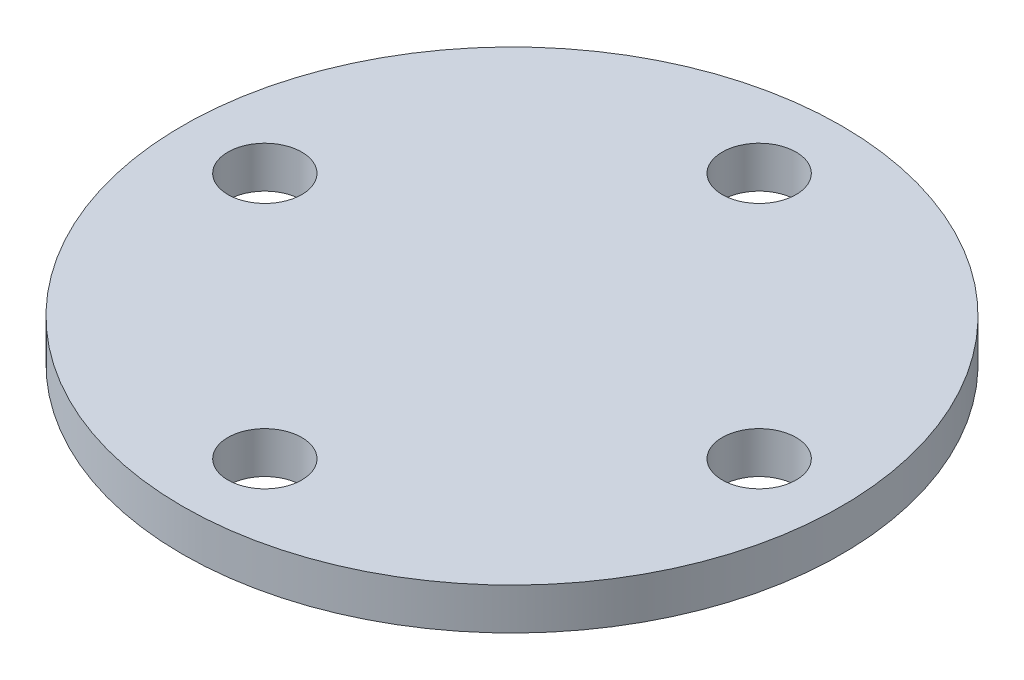
SolidWorks part; units mm, degrees
material "Custom Plastic"
ref_plane "Front Plane" through (0, 0, 0) normal (0, 0, 1) x (1, 0, 0)
ref_plane "Top Plane" through (0, 0, 0) normal (0, 1, 0) x (1, 0, 0)
ref_plane "Right Plane" through (0, 0, 0) normal (1, 0, 0) x (0, 0, -1)
sketch "Sketch1" plane through (0, 0, 0) normal (0, 1, 0) x (1, 0, 0)
  circle A0 centre (0, 0) radius 12.7
  dimension "D1" = 25.4
extrude "Boss-Extrude1" add sketch "Sketch1" along normal blind 1.6002
sketch "Sketch2" plane through (0, 1.6002, 0) normal (0, 1, 0) x (1, 0, 0)
  circle A0 centre (-9.525, 0) radius 1.4224
  dimension "D1" = 2.8448
  dimension "D2" = 9.525
ref_axis "Axis1" through (0, 1.6002, 0) along (0, -1, 0)
extrude "Cut-Extrude1" cut sketch "Sketch2" against normal blind 1.6002
pattern_circular "CirPattern1" count 4 over 360 about axis through (0, 1.6002, 0) along (0, -1, 0) of "Cut-Extrude1"
